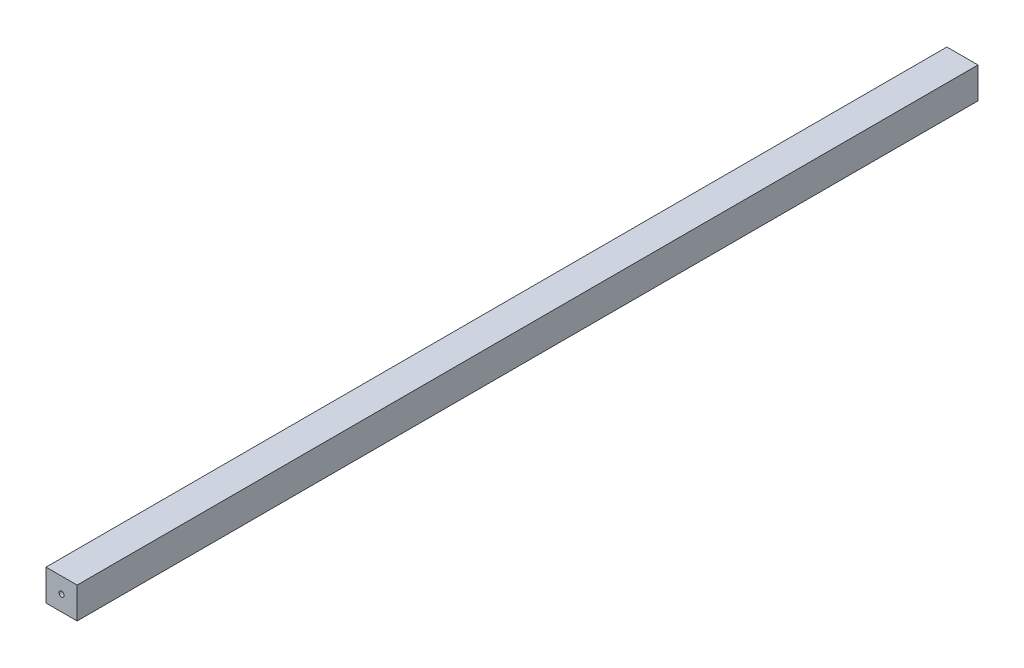
SolidWorks part; units mm, degrees
ref_plane "Front Plane" through (0, 0, 0) normal (0, 0, 1) x (1, 0, 0)
ref_plane "Top Plane" through (0, 0, 0) normal (0, 1, 0) x (1, 0, 0)
ref_plane "Right Plane" through (0, 0, 0) normal (1, 0, 0) x (0, 0, -1)
sketch "Sketch1" plane through (0, 0, 0) normal (0, 0, 1) x (1, 0, 0)
  line L1 (-12.7, -12.7) -> (12.7, -12.7)
  line L2 (-12.7, -12.7) -> (-12.7, 12.7)
  line L3 (-12.7, 12.7) -> (12.7, 12.7)
  line L4 (12.7, -12.7) -> (12.7, 12.7)
  line L5 (-12.7, -12.7) -> (12.7, 12.7) construction
  line L6 (-12.7, 12.7) -> (12.7, -12.7) construction
  point P0 (0, 0)
  dimension "D1" = 25.4
  dimension "D2" = 25.4
extrude "Boss-Extrude1" add sketch "Sketch1" along normal mid plane 735.33
sketch "Sketch2" plane through (0, 0, 367.665) normal (0, 0, 1) x (1, 0, 0)
  circle A0 centre (0, 0) radius 2.0828
  dimension "D1" = 4.1656
extrude "Cut-Extrude1" cut sketch "Sketch2" against normal blind 812.292
